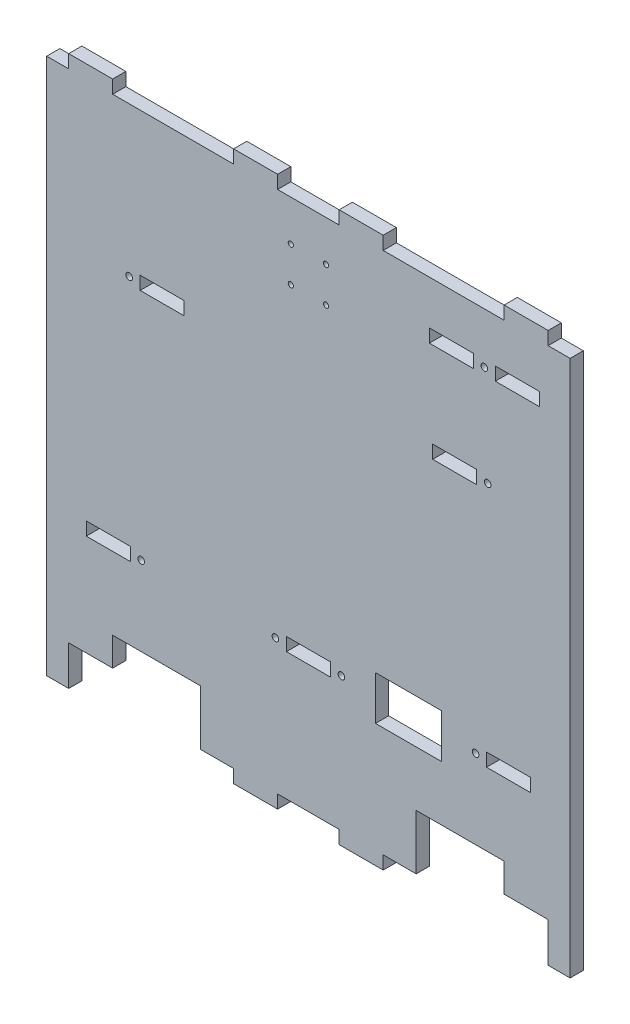
SolidWorks part; units mm, degrees
ref_plane "Plan de face" through (0, 0, 0) normal (0, 0, 1) x (1, 0, 0)
ref_plane "Plan de dessus" through (0, 0, 0) normal (0, 1, 0) x (1, 0, 0)
ref_plane "Plan de droite" through (0, 0, 0) normal (1, 0, 0) x (0, 0, -1)
sketch "Esquisse1" plane through (0, 0, 0) normal (0, 0, 1) x (1, 0, 0)
  line L0 (0, 139.6766) -> (0, -178.3461) construction
  line L1 (-109, 119) -> (109, 119)
  line L2 (-109, 119) -> (-109, -119)
  line L3 (-109, -119) -> (109, -119)
  line L4 (109, 119) -> (109, -119)
  line L5 (-101, -61) -> (-81, -61)
  line L6 (-101, -61) -> (-101, -55)
  line L7 (-101, -55) -> (-81, -55)
  line L8 (-81, -61) -> (-81, -55)
  line L9 (-10, -61) -> (10, -61)
  line L10 (-10, -61) -> (-10, -55)
  line L11 (-10, -55) -> (10, -55)
  line L12 (10, -61) -> (10, -55)
  line L13 (81, -61) -> (101, -61)
  line L14 (81, -61) -> (81, -55)
  line L15 (81, -55) -> (101, -55)
  line L16 (101, -61) -> (101, -55)
  line L17 (-76.5, 54) -> (-56.5, 54)
  line L18 (-76.5, 54) -> (-76.5, 48)
  line L19 (-76.5, 48) -> (-56.5, 48)
  line L20 (-56.5, 54) -> (-56.5, 48)
  line L21 (56.5, 54) -> (76.5, 54)
  line L22 (56.5, 54) -> (56.5, 48)
  line L23 (56.5, 48) -> (76.5, 48)
  line L24 (76.5, 54) -> (76.5, 48)
  line L25 (30.5, -69) -> (60.5, -69)
  line L26 (30.5, -69) -> (30.5, -49)
  line L27 (30.5, -49) -> (60.5, -49)
  line L28 (60.5, -69) -> (60.5, -49)
  line L30 (55, 99) -> (75, 99)
  line L31 (55, 99) -> (55, 93)
  line L32 (55, 93) -> (75, 93)
  line L33 (75, 99) -> (75, 93)
  line L34 (85, 99) -> (105, 99)
  line L35 (85, 99) -> (85, 93)
  line L36 (85, 93) -> (105, 93)
  line L37 (105, 99) -> (105, 93)
  dimension "D1" = 238
  dimension "D2" = 218
  dimension "D3" = 109
  dimension "D4" = 119
  dimension "D5" = 20
  dimension "D6" = 6
  dimension "D7" = 6
  dimension "D8" = 20
  dimension "D9" = 20
  dimension "D10" = 6
  dimension "D11" = 58
  dimension "D12" = 8
  dimension "D13" = 8
  dimension "D14" = 99
  dimension "D15" = 58
  dimension "D16" = 58
  dimension "D17" = 20
  dimension "D18" = 6
  dimension "D19" = 6
  dimension "D20" = 20
  dimension "D21" = 167
  dimension "D22" = 167
  dimension "D23" = 32.5
  dimension "D24" = 32.5
  dimension "D25" = 20
  dimension "D26" = 30
  dimension "D27" = 50
  dimension "D28" = 20.5
  dimension "D29" = 6
  dimension "D30" = 6
  dimension "D31" = 20
  dimension "D32" = 20
  dimension "D33" = 20
  dimension "D34" = 20
  dimension "D35" = 10
  dimension "D36" = 4
extrude "Boss.-Extru.1" add sketch "Esquisse1" along normal blind 6
sketch "Esquisse2" plane through (0, 0, 6) normal (0, 0, 1) x (1, 0, 0)
  line L0 (-109, -119) -> (109, -119) construction
  line L1 (-89, -119) -> (-49, -119)
  line L2 (-89, -119) -> (-89, -94)
  line L3 (-89, -94) -> (-49, -94)
  line L4 (-49, -119) -> (-49, -94)
  line L5 (-109, 119) -> (-109, -119) construction
  line L6 (49, -119) -> (89, -119)
  line L7 (49, -119) -> (49, -94)
  line L8 (49, -94) -> (89, -94)
  line L9 (89, -119) -> (89, -94)
  line L10 (109, -119) -> (109, 119) construction
  dimension "D1" = 40
  dimension "D2" = 20
  dimension "D3" = 40
  dimension "D4" = 20
  dimension "D5" = 25
  dimension "D6" = 25
extrude "Enlèv. mat.-Extru.1" cut sketch "Esquisse2" against normal blind 6
sketch "Esquisse3" plane through (0, 0, 6) normal (0, 0, 1) x (1, 0, 0)
  line L0 (0, 157.5653) -> (0, -190.6765) construction
  line L5 (-49, -119) -> (49, -119) construction
  line L6 (-34, -119) -> (-14, -119)
  line L7 (-34, -119) -> (-34, -125)
  line L8 (-34, -125) -> (-14, -125)
  line L9 (-14, -119) -> (-14, -125)
  line L10 (-49, -119) -> (-49, -94) construction
  line L15 (14, -119) -> (14, -125)
  line L16 (34, -125) -> (14, -125)
  line L17 (34, -119) -> (34, -125)
  line L18 (34, -119) -> (14, -119)
  line L19 (198.2674, 0) -> (-212.4835, 0) construction
  line L20 (0, -157.5653) -> (0, 190.6765) construction
  line L21 (34, 125) -> (14, 125)
  line L22 (14, 119) -> (14, 125)
  line L23 (89, 125) -> (109, 125)
  line L24 (89, 125) -> (89, 119)
  line L25 (89, 119) -> (109, 119)
  line L26 (109, 125) -> (109, 119)
  line L27 (-14, 119) -> (-14, 125)
  line L28 (-34, 125) -> (-14, 125)
  line L29 (-34, 119) -> (-34, 125)
  line L30 (-34, 119) -> (-14, 119)
  line L31 (-109, 125) -> (-109, 119)
  line L32 (-89, 119) -> (-109, 119)
  line L33 (-89, 125) -> (-89, 119)
  line L34 (-89, 125) -> (-109, 125)
  line L35 (34, 119) -> (14, 119)
  line L36 (34, 119) -> (34, 125)
  dimension "D2" = 20
  dimension "D3" = 6
  dimension "D4" = 15
extrude "Boss.-Extru.3" add sketch "Esquisse3" against normal blind 6
sketch "Esquisse4" plane through (0, 0, 6) normal (0, 0, 1) x (1, 0, 0)
  line L0 (-111.0944, 51) -> (126.4062, 51) construction
  line L1 (116.6655, -58) -> (-122.9189, -58) construction
  line L2 (76.5, 48) -> (76.5, 54) construction
  line L3 (0, 153.5677) -> (0, -173.1111) construction
  line L4 (45.0686, 96) -> (109.1297, 96) construction
  line L5 (81, -55) -> (81, -61) construction
  line L6 (10, -61) -> (10, -55) construction
  line L7 (-10, -55) -> (-10, -61) construction
  line L8 (75, 93) -> (75, 99) construction
  line L10 (-56.5, 54) -> (-76.5, 54) construction
  line L13 (55, 93) -> (75, 93) construction
  circle A0 centre (-15, -58) radius 1.5
  circle A1 centre (-76, -58) radius 1.5
  circle A2 centre (80, 96) radius 1.5
  circle A3 centre (81.5, 51) radius 1.5
  circle A4 centre (76, -58) radius 1.5
  circle A5 centre (15, -58) radius 1.5
  circle A6 centre (-81.5, 51) radius 1.5
  dimension "D2" = 5
  dimension "D4" = 3
  dimension "D5" = 5
  dimension "D6" = 5
  dimension "D7" = 3
  dimension "D8" = 3
  dimension "D9" = 3
  dimension "D10" = 5
  dimension "D11" = 3
  dimension "D12" = 5
  dimension "D15" = 3
  dimension "D14" = 3
extrude "Enlèv. mat.-Extru.2" cut sketch "Esquisse4" against normal blind 6
sketch "Esquisse5" plane through (0, 0, 6) normal (0, 0, 1) x (1, 0, 0)
  line L0 (-109, 119) -> (-109, -125)
  line L1 (-109, 119) -> (-119, 119)
  line L2 (-109, -125) -> (-119, -125)
  line L3 (-119, 119) -> (-119, -125)
  line L5 (109, -125) -> (109, 119)
  line L6 (109, -125) -> (119, -125)
  line L7 (109, 119) -> (119, 119)
  line L8 (119, -125) -> (119, 119)
  line L11 (109, 125) -> (89, 125) construction
  line L12 (-89, 125) -> (-109, 125) construction
  dimension "D1" = 10
  dimension "D2" = 10
  dimension "D3" = 244
  dimension "D4" = 244
  dimension "D5" = 6
  dimension "D6" = 6
extrude "Boss.-Extru.4" add sketch "Esquisse5" against normal blind 6
sketch "Esquisse6" plane through (0, 0, 6) normal (0, 0, 1) x (1, 0, 0)
  line L0 (0, 108.4917) -> (0, -172.5759) construction
  line L1 (89, -119) -> (109, -119)
  line L2 (89, -119) -> (89, -107)
  line L3 (89, -107) -> (109, -107)
  line L4 (109, -119) -> (109, -107)
  line L5 (-109, -119) -> (-109, -107)
  line L6 (-89, -107) -> (-109, -107)
  line L7 (-89, -119) -> (-89, -107)
  line L8 (-89, -119) -> (-109, -119)
  dimension "D1" = 12
  dimension "D2" = 20
extrude "Enlèv. mat.-Extru.3" cut sketch "Esquisse6" against normal blind 6
sketch "Esquisse7" plane through (0, 0, 6) normal (0, 0, 1) x (1, 0, 0)
  line L0 (14, 119) -> (-14, 119) construction
  line L1 (14, 125) -> (14, 119) construction
  circle A0 centre (-8, 100.5) radius 1.175
  circle A1 centre (8, 100.5) radius 1.175
  circle A2 centre (-8, 84.5) radius 1.175
  circle A3 centre (8, 84.5) radius 1.175
  dimension "D1" = 16
  dimension "D7" = 2.35
  dimension "D8" = 2.35
  dimension "D9" = 2.35
  dimension "D10" = 2.35
  dimension "D2" = 16
  dimension "D3" = 16
  dimension "D4" = 16
  dimension "D5" = 18.5
  dimension "D6" = 6
  dimension "D11" = 18.5
extrude "Enlèv. mat.-Extru.4" cut sketch "Esquisse7" against normal through all
equation "\"D3@Esquisse1\"=\"D2@Esquisse1\"/2"
equation "\"D4@Esquisse1\"=\"D1@Esquisse1\"/2"
